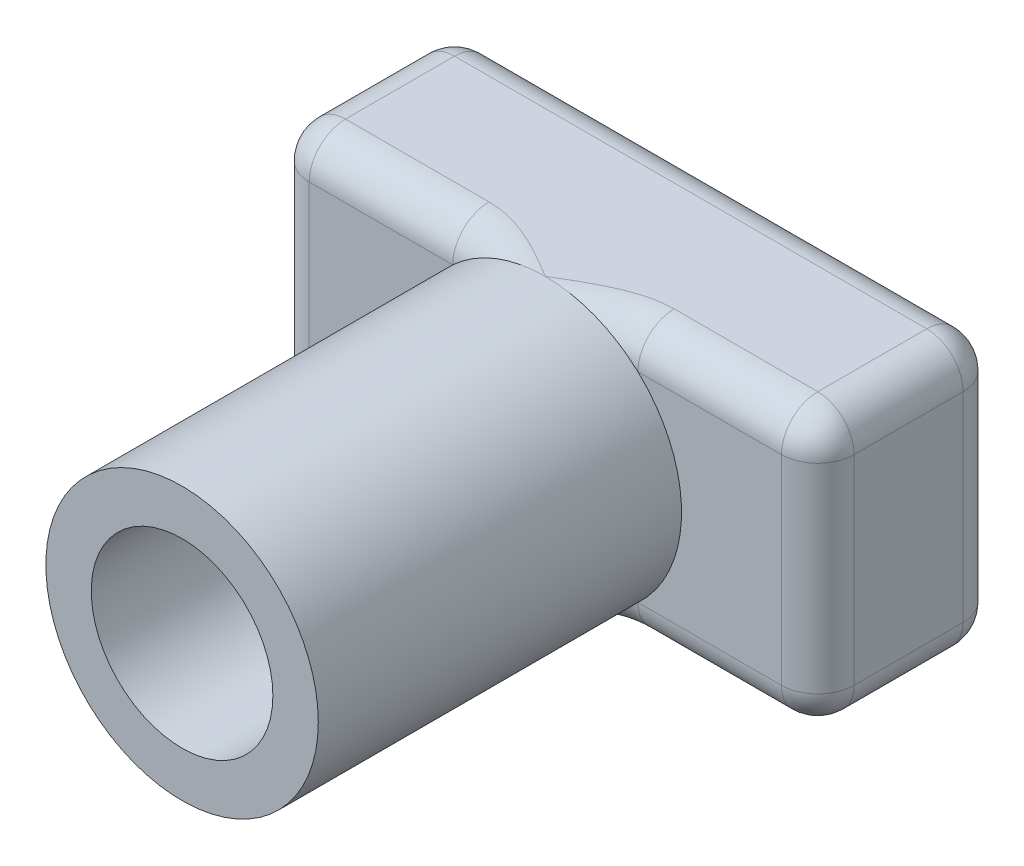
SolidWorks part; units mm, degrees
ref_plane "Front Plane" through (0, 0, 0) normal (0, 0, 1) x (1, 0, 0)
ref_plane "Top Plane" through (0, 0, 0) normal (0, 1, 0) x (1, 0, 0)
ref_plane "Right Plane" through (0, 0, 0) normal (1, 0, 0) x (0, 0, -1)
sketch "Sketch1" plane through (0, 0, 0) normal (0, 0, 1) x (1, 0, 0)
  circle A0 centre (0, 0) radius 5
  circle A1 centre (0, 0) radius 7.5
  point P0 (0, 0)
  dimension "D1" = 10
  dimension "D2" = 15
extrude "Boss-Extrude1" add sketch "Sketch1" along normal blind 20
sketch "Sketch2" plane through (0, 0, 0) normal (0, 0, -1) x (-1, 0, 0)
  line L1 (-15, 7.5) -> (15, 7.5)
  line L2 (-15, 7.5) -> (-15, -7.5)
  line L3 (-15, -7.5) -> (15, -7.5)
  line L4 (15, 7.5) -> (15, -7.5)
  line L5 (-15, 7.5) -> (15, -7.5) construction
  line L6 (-15, -7.5) -> (15, 7.5) construction
  circle A0 centre (0, 0) radius 7.5 construction
  point P0 (0, 0)
  dimension "D1" = 30
extrude "Boss-Extrude2" add sketch "Sketch2" along normal blind 10
fillet "Fillet1" radius 2 14 edges at (15, 0, -10) (15, 0, 0) (15, -7.5, -5) (0, -7.5, -10) (-7.5, -7.5, 0) (7.5, -7.5, 0) (0, 7.5, -10) (15, 7.5, -5) (7.5, 7.5, 0) (-7.5, 7.5, 0) (-15, -7.5, -5) (-15, 0, -10) (-15, 7.5, -5) (-15, 0, 0)
